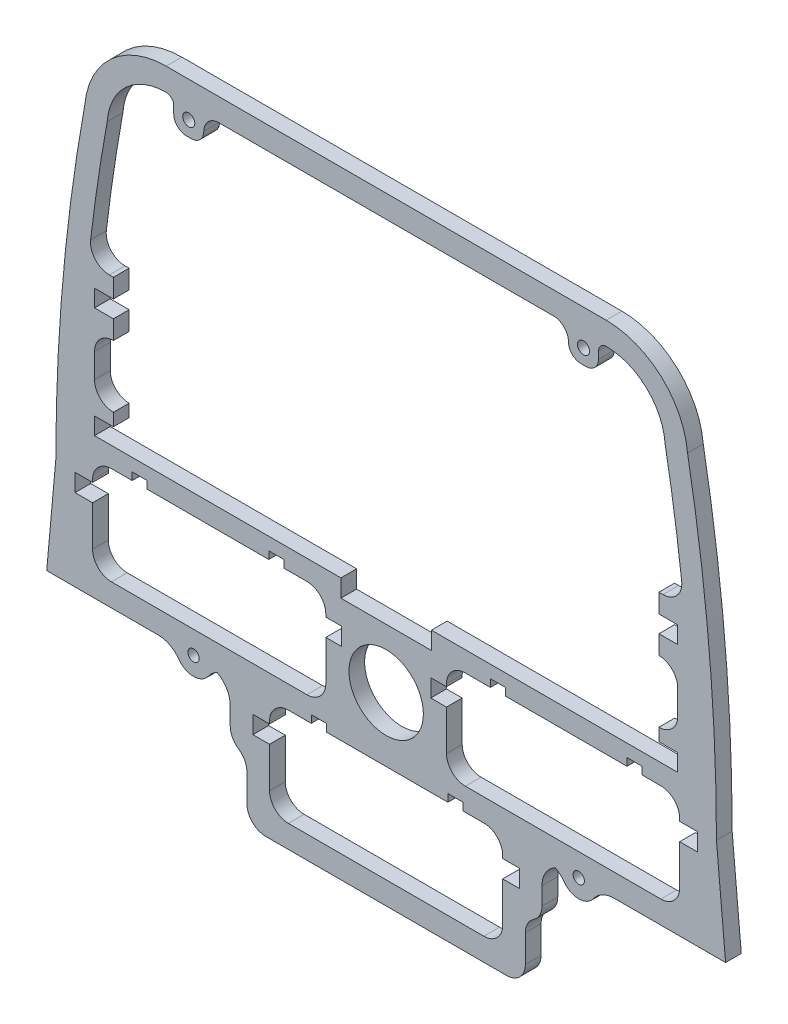
SolidWorks part; units mm, degrees
material "Delrin 2700 NC010, Low Viscosity Acetal Copolymer (SS)"
ref_plane "Front Plane" through (0, 0, 0) normal (0, 0, 1) x (1, 0, 0)
ref_plane "Top Plane" through (0, 0, 0) normal (0, 1, 0) x (1, 0, 0)
ref_plane "Right Plane" through (0, 0, 0) normal (1, 0, 0) x (0, 0, -1)
sketch "Sketch1" plane through (0, 0, 0) normal (0, 0, 1) x (1, 0, 0)
  line L0 (33.3676, -11.9888) -> (34.29, -22.225)
  line L1 (22.225, 27.94) -> (-22.225, 27.94)
  line L2 (-34.29, -22.225) -> (-30.4467, 20.4259) construction
  line L3 (-33.3676, -11.9888) -> (-33.3676, 14.6458) construction
  line L4 (-33.3676, -11.9888) -> (-34.29, -22.225)
  line L5 (16.9079, 25.654) -> (-16.9079, 25.654)
  line L6 (6.096, -13.97) -> (6.096, -19.939)
  line L7 (-29.6529, -19.939) -> (-6.096, -19.939)
  line L8 (-34.29, -22.225) -> (-21.299, -22.225)
  line L9 (-29.6529, -10.033) -> (-29.6529, -12.192)
  line L10 (18.4213, 24.1407) -> (18.4213, 24.1363)
  line L11 (19.6913, 22.8663) -> (20.1867, 22.8663)
  line L12 (21.4567, 24.1363) -> (21.4567, 24.8713)
  line L13 (-21.4567, 24.1363) -> (-21.4567, 24.8713)
  line L14 (-19.6913, 22.8663) -> (-20.1867, 22.8663)
  line L15 (-18.4213, 24.1407) -> (-18.4213, 24.1363)
  line L16 (29.4572, -8.001) -> (4.572, -8.001)
  line L17 (29.6529, -10.033) -> (25.8579, -10.033)
  line L18 (0, 18.415) -> (0, -18.415) construction
  line L19 (-1007.9925, 0) -> (48992.0075, 0) construction
  line L20 (-6.096, -10.033) -> (-10.3339, -10.033)
  line L21 (19.939, 24.384) -> (21.4567, 24.384) construction
  line L22 (6.096, -19.939) -> (29.6529, -19.939)
  line L23 (-6.096, -10.033) -> (-6.096, -12.192)
  line L24 (5.9491, -2.2098) -> (59.5431, -2.2098) construction
  line L25 (5.9491, -2.2098) -> (5.9491, -11.9888) construction
  line L26 (3.4091, -11.9888) -> (-3.4091, -11.9888) construction
  line L27 (59.5431, -2.2098) -> (59.5431, -11.9888) construction
  line L28 (-31.7887, -19.939) -> (31.7887, -19.939) construction
  line L29 (22.225, 25.654) -> (-22.225, 25.654) construction
  line L30 (-6.096, -19.939) -> (-6.1666, -19.9899)
  line L31 (29.4572, -6.2738) -> (27.5522, -6.2738)
  line L32 (27.5522, -6.2738) -> (27.5522, -5.0038)
  line L33 (-29.6529, -12.192) -> (-31.4309, -12.192)
  line L34 (27.5522, -5.0038) -> (29.4572, -5.0038)
  line L35 (29.4572, 1.27) -> (27.5522, 1.27)
  line L36 (27.5522, 1.27) -> (27.5522, 3.175)
  line L37 (27.5522, 3.175) -> (29.4572, 3.175)
  line L38 (29.4572, 4.9022) -> (27.5522, 4.9022)
  line L39 (19.939, 24.384) -> (18.4213, 24.384) construction
  line L40 (27.5522, 4.9022) -> (27.5522, 6.8072)
  line L41 (27.5522, 6.8072) -> (30.0922, 6.8072)
  line L42 (19.939, 24.384) -> (19.939, 22.8663) construction
  line L43 (6.096, -10.033) -> (6.096, -12.192)
  line L44 (-29.4572, -6.2738) -> (-29.4572, -8.001)
  line L45 (-29.4572, -6.2738) -> (-27.5522, -6.2738)
  line L46 (-27.5522, -6.2738) -> (-27.5522, -5.0038)
  line L47 (-27.5522, -5.0038) -> (-29.4572, -5.0038)
  line L48 (-29.4572, 1.27) -> (-29.4572, -5.0038)
  line L49 (-29.4572, 1.27) -> (-27.5522, 1.27)
  line L50 (-27.5522, 1.27) -> (-27.5522, 3.175)
  line L51 (-27.5522, 3.175) -> (-29.4572, 3.175)
  line L52 (-29.4572, 4.9022) -> (-29.4572, 3.175)
  line L53 (-31.4309, -12.192) -> (-31.4309, -13.97)
  line L54 (-31.4309, -13.97) -> (-29.6529, -13.97)
  line L55 (-6.096, -12.192) -> (-4.5069, -12.192)
  line L56 (-4.5069, -12.192) -> (-4.5069, -13.97)
  line L57 (-4.5069, -13.97) -> (-6.096, -13.97)
  line L58 (-29.6529, -10.033) -> (-29.6529, -19.939) construction
  line L59 (-29.6529, -14.986) -> (-33.4249, -14.986) construction
  line L60 (-29.6529, -14.986) -> (-0.4824, -14.986) construction
  line L61 (-6.096, -13.97) -> (-6.096, -19.939)
  line L62 (-29.6529, -19.939) -> (-29.6529, -13.97)
  line L63 (29.6529, -19.939) -> (29.6529, -13.97)
  line L64 (-31.0816, -12.0913) -> (-31.7887, -19.939) construction
  line L65 (29.6529, -10.033) -> (29.6529, -12.192)
  line L66 (31.4309, -13.97) -> (29.6529, -13.97)
  line L67 (31.4309, -12.192) -> (31.4309, -13.97)
  line L68 (29.6529, -12.192) -> (31.4309, -12.192)
  line L69 (6.096, -12.192) -> (4.5069, -12.192)
  line L70 (4.5069, -12.192) -> (4.5069, -13.97)
  line L71 (4.5069, -13.97) -> (6.096, -13.97)
  line L72 (29.4572, 4.9022) -> (29.4572, 3.175)
  line L73 (31.0816, -12.0913) -> (31.7887, -19.939) construction
  line L74 (29.4572, 1.27) -> (29.4572, -5.0038)
  line L75 (29.4572, -6.2738) -> (29.4572, -8.001)
  line L76 (-29.4572, 4.9022) -> (-27.5522, 4.9022)
  line L77 (-27.5522, 4.9022) -> (-27.5522, 6.8072)
  line L78 (-27.5522, 6.8072) -> (-30.0922, 6.8072)
  line L79 (-17.616, -22.225) -> (-15.7485, -22.225)
  line L80 (21.299, -22.225) -> (34.29, -22.225)
  line L81 (-34.29, -22.225) -> (34.29, -22.225) construction
  line L82 (-4.572, -8.001) -> (-4.572, -9.779)
  line L83 (-4.572, -9.779) -> (0, -9.779)
  line L84 (0, -9.779) -> (4.572, -9.779)
  line L85 (4.572, -9.779) -> (4.572, -8.001)
  line L86 (-4.572, -8.001) -> (-29.4572, -8.001)
  line L87 (-11.7784, -22.225) -> (-11.7784, -24.384)
  line L88 (-11.7784, -24.384) -> (-13.4625, -24.384)
  line L89 (-13.4625, -24.384) -> (-13.4625, -26.162)
  line L90 (-13.4625, -26.162) -> (-11.7784, -26.162)
  line L91 (-11.7784, -26.162) -> (-11.7784, -32.131)
  line L92 (-11.7784, -32.131) -> (11.7784, -32.131)
  line L93 (11.7784, -32.131) -> (11.7784, -26.162)
  line L94 (11.7784, -26.162) -> (13.4625, -26.162)
  line L95 (13.4625, -26.162) -> (13.4625, -24.384)
  line L96 (13.4625, -24.384) -> (11.7784, -24.384)
  line L97 (11.7784, -24.384) -> (11.7784, -22.225)
  line L98 (11.7784, -22.225) -> (-11.7784, -22.225) construction
  line L99 (0, -32.131) -> (0, -22.225) construction
  line L100 (-11.7784, -22.225) -> (-7.562, -22.225)
  line L101 (-15.7485, -22.098) -> (-15.7485, -28.448) construction
  line L102 (-15.7485, -22.225) -> (-15.7485, -28.448)
  line L103 (-15.7485, -28.448) -> (-14.0644, -28.448)
  line L104 (-14.0644, -28.448) -> (-14.0644, -34.417)
  line L105 (-14.0644, -34.417) -> (14.0644, -34.417)
  line L106 (14.0644, -34.417) -> (14.0644, -28.448)
  line L107 (14.0644, -28.448) -> (15.7485, -28.448)
  line L108 (15.7485, -28.448) -> (15.7485, -22.225)
  line L109 (15.7485, -22.225) -> (17.616, -22.225)
  line L110 (15.7485, -28.448) -> (15.7485, -22.098) construction
  line L111 (15.7485, -22.098) -> (14.0609, -22.098) construction
  line L112 (14.0609, -22.098) -> (14.0609, -22.098) construction
  line L113 (-14.0609, -22.098) -> (-14.0609, -22.098) construction
  line L114 (-14.0609, -22.098) -> (-15.7485, -22.098) construction
  line L115 (-11.8579, -10.033) -> (-24.1339, -10.033)
  line L116 (7.762, -22.2885) -> (6.238, -22.2885) construction
  line L117 (12.0579, -10.1918) -> (10.5339, -10.1918) construction
  line L118 (-24.1339, -10.1917) -> (-25.6579, -10.1917) construction
  line L119 (-25.6579, -10.033) -> (-29.6529, -10.033)
  line L120 (10.5339, -10.033) -> (6.096, -10.033)
  line L121 (-10.3339, -10.1917) -> (-11.8579, -10.1917) construction
  line L122 (25.8579, -10.1918) -> (24.3339, -10.1918) construction
  line L123 (24.3339, -10.033) -> (12.0579, -10.033)
  line L124 (7.762, -22.225) -> (11.7784, -22.225)
  line L125 (12.0579, -10.1918) -> (10.5339, -10.1918) construction
  line L126 (-24.1339, -10.1917) -> (-25.6579, -10.1917) construction
  line L127 (-6.038, -22.225) -> (6.238, -22.225)
  line L136 (-10.3339, -10.1917) -> (-11.8579, -10.1917) construction
  line L137 (25.8579, -10.1918) -> (24.3339, -10.1918) construction
  line L138 (-25.6579, -10.1917) -> (-25.6579, -9.271)
  line L139 (-25.6579, -9.271) -> (-24.1339, -9.271)
  line L140 (-24.1339, -9.271) -> (-24.1339, -10.1917)
  line L141 (-11.8579, -10.1917) -> (-11.8579, -9.271)
  line L142 (-11.8579, -9.271) -> (-10.3339, -9.271)
  line L143 (-10.3339, -9.271) -> (-10.3339, -10.1917)
  line L144 (10.5339, -10.1918) -> (10.5339, -9.271)
  line L145 (10.5339, -9.271) -> (12.0579, -9.271)
  line L146 (12.0579, -9.271) -> (12.0579, -10.1918)
  line L147 (24.3339, -10.1918) -> (24.3339, -9.271)
  line L152 (7.762, -22.2885) -> (6.238, -22.2885) construction
  line L153 (-6.038, -22.2885) -> (-7.562, -22.2885) construction
  line L154 (-6.038, -22.2885) -> (-7.562, -22.2885) construction
  line L155 (24.3339, -9.271) -> (25.8579, -9.271)
  line L156 (25.8579, -9.271) -> (25.8579, -10.1918)
  line L157 (-7.562, -22.2885) -> (-7.562, -21.463)
  line L158 (-7.562, -21.463) -> (-6.038, -21.463)
  line L159 (-6.038, -21.463) -> (-6.038, -22.2885)
  line L160 (6.238, -22.2885) -> (6.238, -21.463)
  line L161 (6.238, -21.463) -> (7.762, -21.463)
  line L162 (7.762, -21.463) -> (7.762, -22.2885)
  arc A0 (22.225, 27.94) -> (30.4467, 20.4259) centre (22.225, 19.685) cw
  arc A1 (-22.225, 27.94) -> (-30.4467, 20.4259) centre (-22.225, 19.685) ccw
  arc A2 (33.3676, -11.9888) -> (30.4467, 20.4259) centre (-147.9525, -11.9888) ccw
  circle A3 centre (0, -15.748) radius 3.7592
  circle A4 centre (19.4575, -22.225) radius 0.5715
  arc A5 (-33.3676, -11.9888) -> (-30.4467, 20.4259) centre (147.9525, -11.9888) cw
  arc A6 (-17.616, -22.225) -> (-21.299, -22.225) centre (-19.4575, -22.225) cw
  arc A7 (17.616, -22.225) -> (21.299, -22.225) centre (19.4575, -22.225) ccw
  arc A8 (20.1867, 22.8663) -> (21.4567, 24.1363) centre (20.1867, 24.1363) ccw
  circle A9 centre (-19.939, 24.384) radius 0.6096
  circle A10 centre (19.939, 24.384) radius 0.6096
  arc A11 (18.4213, 24.1363) -> (19.6913, 22.8663) centre (19.6913, 24.1363) ccw
  circle A12 centre (-19.4575, -22.225) radius 0.5715
  arc A13 (18.4213, 24.1407) -> (16.9079, 25.654) centre (16.9079, 24.1407) ccw
  arc A14 (22.2416, 25.654) -> (21.4567, 24.8713) centre (22.2394, 24.8713) ccw
  arc A15 (-22.2416, 25.654) -> (-21.4567, 24.8713) centre (-22.2394, 24.8713) cw
  arc A16 (-20.1867, 22.8663) -> (-21.4567, 24.1363) centre (-20.1867, 24.1363) cw
  arc A17 (-18.4213, 24.1363) -> (-19.6913, 22.8663) centre (-19.6913, 24.1363) cw
  arc A18 (-22.2416, 25.654) -> (-28.1777, 20.1262) centre (-22.225, 19.685) ccw
  arc A19 (-18.4213, 24.1407) -> (-16.9079, 25.654) centre (-16.9079, 24.1407) cw
  arc A20 (31.0816, -12.0913) -> (31.0816, -11.9888) centre (-147.9525, -11.9888) ccw
  circle A21 centre (-19.4575, -22.225) radius 1.8415 construction
  arc A23 (22.2416, 25.654) -> (28.1777, 20.1262) centre (22.225, 19.685) cw
  arc A25 (-22.225, 25.654) -> (-28.1777, 20.1262) centre (-22.225, 19.685) ccw construction
  arc A26 (22.225, 25.654) -> (28.1777, 20.1262) centre (22.225, 19.685) cw construction
  arc A28 (-31.0816, -12.0913) -> (-28.1777, 20.1262) centre (147.9525, -11.9888) cw construction
  arc A30 (31.0816, -12.0913) -> (28.1777, 20.1262) centre (-147.9525, -11.9888) ccw construction
  arc A31 (30.0922, 6.8072) -> (28.1777, 20.1262) centre (-147.9525, -11.9888) ccw
  arc A33 (-30.0922, 6.8072) -> (-28.1777, 20.1262) centre (147.9525, -11.9888) cw
  point P0 (0, 0)
  point P1 (0, 27.94)
  point P31 (0, -11.9888)
  point P121 (-30.9018, -14.986)
  point P135 (-17.616, -22.225)
  dimension "D4" = 2.286
  dimension "D6" = 8.255
  dimension "D7" = 19.4575
  dimension "D8" = 50.165
  dimension "D9" = 15.748
  dimension "D5" = 1.2192
  dimension "D17" = 1.143
  dimension "D3" = 7.5184
  dimension "D18" = 1.27
  dimension "D19" = 1.27
  dimension "D26" = 11.176
  dimension "D28" = 0.7827
  dimension "D29" = 1.5133
  dimension "D32" = 1.778
  dimension "D2" = 44.45
  dimension "D10" = 1.27
  dimension "D11" = 1.27
  dimension "D12" = 68.58
  dimension "D13" = 19.939
  dimension "D14" = 22.225
  dimension "D15" = 53.594
  dimension "D16" = 9.779
  dimension "D20" = 6.096
  dimension "D21" = 11.938
  dimension "D22" = 2.032
  dimension "D23" = 1.7272
  dimension "D24" = 1.27
  dimension "D25" = 1.905
  dimension "D27" = 0.4954
  dimension "D30" = 1.905
  dimension "D31" = 1.7272
  dimension "D33" = 1.778
  dimension "D34" = 2.159
  dimension "D35" = 23.5569
  dimension "D36" = 26.924
  dimension "D37" = 1.905
  dimension "D38" = 2.54
  dimension "D39" = 1.778
  dimension "D40" = 9.144
  dimension "D42" = 0.762
  dimension "D43" = 0.762
  dimension "D44" = 1.684
  dimension "D41" = 2.286
extrude "Boss-Extrude1" add sketch "Sketch1" along normal blind 1.5875 contours L8 A12 A4 L0 A2 A0 L1 A1 A5 L4 L74 L16 A18 A15 L13 A16 L14 A17 L15 A19 L5 A13 L10 A11 L11 A8 L12 A14 A23 A20 L22 L43 L17 A10 A9 A3 L20 region at (32.9056, -17.1901, 0)
ref_axis "Axis1" through (0, -15.748, 0) along (0, 0, 1)
fillet "Fillet1" radius 1.905 12 edges at (-6.096, -10.033, 0.7937) (-6.096, -19.939, 0.7937) (-29.6529, -19.939, 0.7937) (6.096, -19.939, 0.7937) (29.6529, -19.939, 0.7937) (29.6529, -10.033, 0.7937) (11.7784, -32.131, 0.7937) (-11.7784, -32.131, 0.7937) (-11.7784, -22.225, 0.7937) (11.7784, -22.225, 0.7937) (6.096, -10.033, 0.7937) (-29.6529, -10.033, 0.7937)
fillet "Fillet2" radius 1.905 6 edges at (-29.4572, 1.27, 0.7937) (-29.4572, -5.0038, 0.7937) (-30.0922, 6.8072, 0.7937) (29.4572, -5.0038, 0.7937) (29.4572, 1.27, 0.7937) (30.0922, 6.8072, 0.7937)
fillet "Fillet3" radius 2.54 6 edges at (-17.616, -22.225, 0.7937) (-21.299, -22.225, 0.7937) (21.299, -22.225, 0.7937) (17.616, -22.225, 0.7937) (15.7485, -22.225, 0.7937) (-15.7485, -22.225, 0.7937)
fillet "Fillet4" radius 1.905 4 edges at (15.7485, -28.448, 0.7937) (14.0644, -34.417, 0.7937) (-14.0644, -34.417, 0.7937) (-15.7485, -28.448, 0.7937)
fillet "Fillet5" radius 1.905 2 edges at (14.0644, -28.448, 0.7937) (-14.0644, -28.448, 0.7937)
